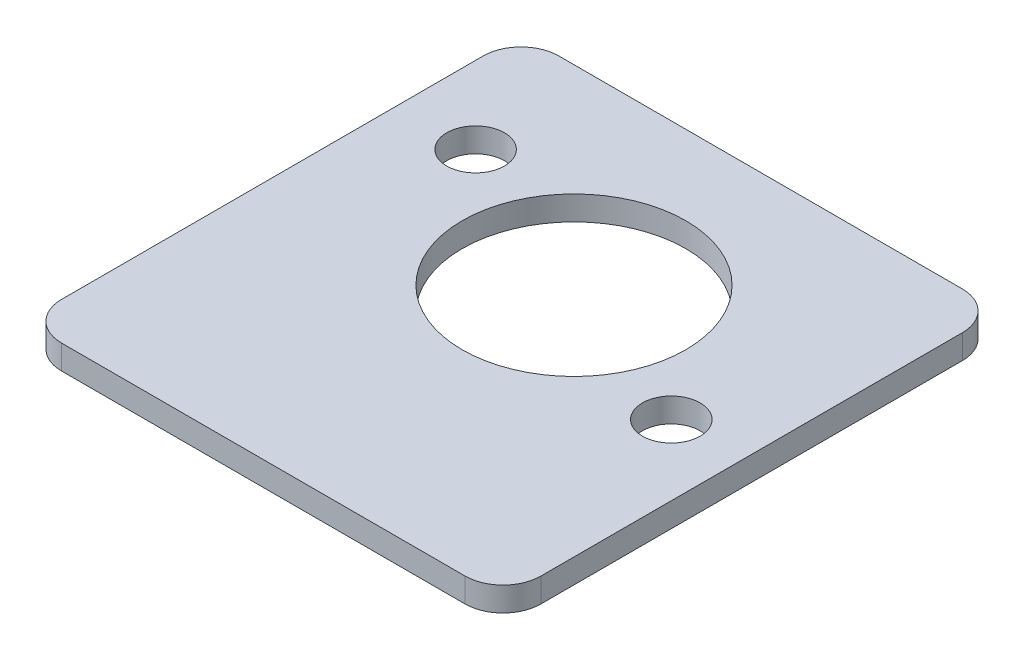
SolidWorks part; units mm, degrees
ref_plane "Front Plane" through (0, 0, 0) normal (0, 0, 1) x (1, 0, 0)
ref_plane "Top Plane" through (0, 0, 0) normal (0, 1, 0) x (1, 0, 0)
ref_plane "Right Plane" through (0, 0, 0) normal (1, 0, 0) x (0, 0, -1)
sketch "Sketch1" plane through (0, 0, 0) normal (0, 1, 0) x (1, 0, 0)
  line L0 (22.61, -1.42) -> (-21.47, 16.66) construction
  line L1 (31.66, -32.85) -> (-31.66, -32.85)
  line L2 (31.66, -32.85) -> (31.66, 32.85)
  line L3 (31.66, 32.85) -> (-31.66, 32.85)
  line L4 (-31.66, -32.85) -> (-31.66, 32.85)
  line L5 (31.66, -32.85) -> (-31.66, 32.85) construction
  line L6 (31.66, 32.85) -> (-31.66, -32.85) construction
  circle A0 centre (0.57, 7.62) radius 14.77
  circle A1 centre (-21.47, 16.66) radius 3.81
  circle A2 centre (22.3659, -1.3199) radius 3.81
  point P0 (0, 0)
  point P8 (0.57, -7.15)
  point P9 (15.34, 7.62)
  point P14 (-21.47, 12.85)
  point P15 (-17.66, 16.66)
  point P18 (0.57, 7.62)
  point P19 (-24.995, 18.1058)
  point P20 (25.8909, -2.7657)
  dimension "D5" = 29.54
  dimension "D8" = 7.62
  dimension "D1" = 63.32
  dimension "D2" = 65.7
  dimension "D3" = 40
  dimension "D4" = 47
  dimension "D6" = 55
extrude "Boss-Extrude1" add sketch "Sketch1" along normal blind 3.2
sketch "Sketch2" plane through (0, 3.2, 0) normal (0, 1, 0) x (1, 0, 0)
  line L1 (26.66, -32.85) -> (-26.66, -32.85)
  line L2 (31.66, -27.85) -> (31.66, 27.85)
  line L3 (26.66, 32.85) -> (-26.66, 32.85)
  line L4 (-31.66, -27.85) -> (-31.66, 27.85)
  line L5 (31.66, -32.85) -> (-31.66, 32.85) construction
  line L6 (31.66, 32.85) -> (-31.66, -32.85) construction
  arc A0 (31.66, 27.85) -> (26.66, 32.85) centre (26.66, 27.85) ccw
  arc A1 (26.66, -32.85) -> (31.66, -27.85) centre (26.66, -27.85) ccw
  arc A2 (-26.66, -32.85) -> (-31.66, -27.85) centre (-26.66, -27.85) cw
  arc A3 (-26.66, 32.85) -> (-31.66, 27.85) centre (-26.66, 27.85) ccw
  point P0 (0, 0)
  dimension "D1" = 5
extrude "Cut-Extrude1" cut sketch "Sketch2" against normal up to surface (3.2 mm away) flip side to cut up to face at (0, 0, 0)
